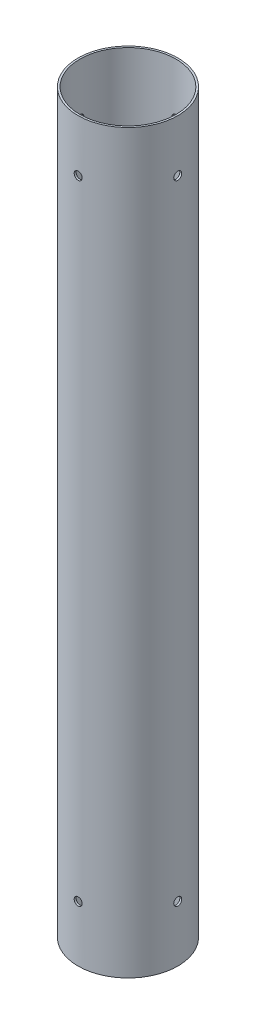
SolidWorks part; units mm, degrees
material "S-Glass Fiber"
ref_plane "Front Plane" through (0, 0, 0) normal (0, 0, 1) x (1, 0, 0)
ref_plane "Top Plane" through (0, 0, 0) normal (0, 1, 0) x (1, 0, 0)
ref_plane "Right Plane" through (0, 0, 0) normal (1, 0, 0) x (0, 0, -1)
sketch "Sketch4" plane through (0, 0, 0) normal (0, 1, 0) x (1, 0, 0)
  circle A0 centre (0, 0) radius 39.6
  circle A1 centre (0, 0) radius 38.1
  point P2 (0, 0)
  point P3 (-0.4699, 0)
  dimension "D1" = 79.2
  dimension "D2" = 76.2
extrude "Boss-Extrude2" add sketch "Sketch4" along normal blind 584.2
sketch "Sketch5" plane through (0, 0, 0) normal (1, 0, 0) x (0, 0, -1)
  line L0 (-39.6, 0) -> (39.6, 0) construction
  circle A0 centre (0, 44.45) radius 3.175
  dimension "D2" = 6.35
  dimension "D1" = 44.45
extrude "Cut-Extrude1" cut sketch "Sketch5" against normal through all
pattern_circular "CirPattern1" count 4 over 360 about axis through (0, 584.2, 0) along (0, -1, 0) of "Cut-Extrude1" reverse direction yes
sketch "Sketch6" plane through (0, 0, 0) normal (1, 0, 0) x (0, 0, -1)
  line L0 (39.6, 584.2) -> (-39.6, 584.2) construction
  circle A0 centre (0, 542.925) radius 3.175
  point P4 (0, 0)
  dimension "D2" = 6.35
  dimension "D1" = 41.275
extrude "Cut-Extrude2" cut sketch "Sketch6" along normal through all
pattern_circular "CirPattern2" count 4 over 360 about axis through (0, 584.2, 0) along (0, -1, 0) of "Cut-Extrude2"
